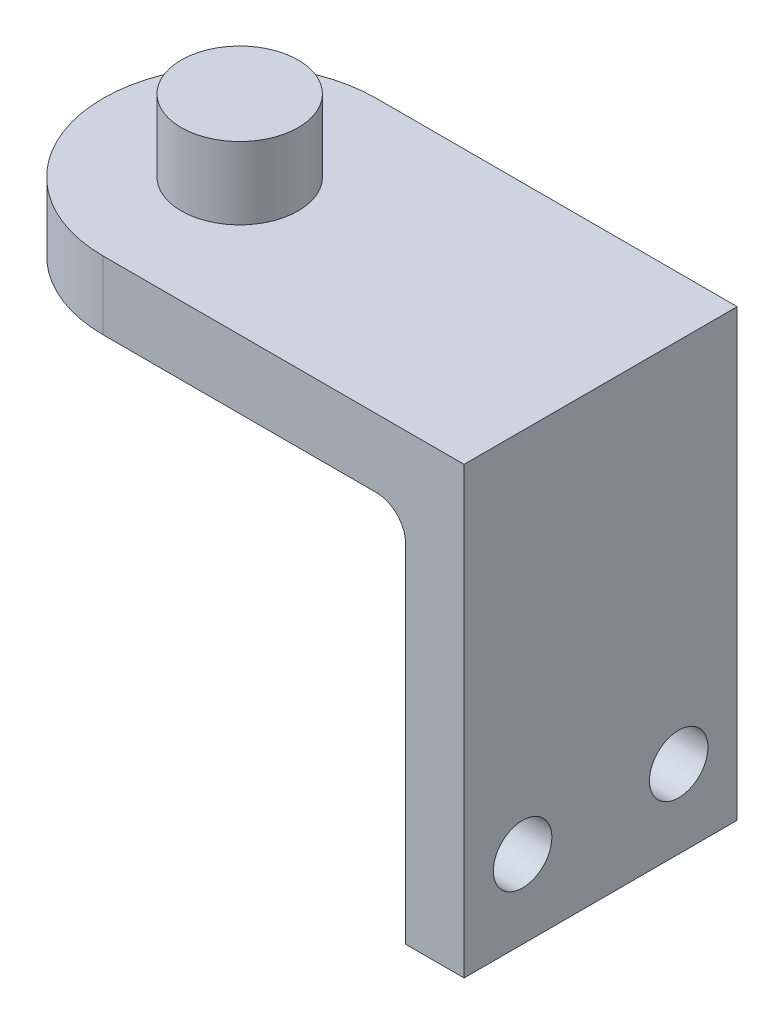
SolidWorks part; units mm, degrees
material "ABS"
ref_plane "Front Plane" through (0, 0, 0) normal (0, 0, 1) x (1, 0, 0)
ref_plane "Top Plane" through (0, 0, 0) normal (0, 1, 0) x (1, 0, 0)
ref_plane "Right Plane" through (0, 0, 0) normal (1, 0, 0) x (0, 0, -1)
ref_plane "Y+19_30" through (0, 19.3, 0) normal (0, 1, 0) x (1, 0, 0)
sketch "Sketch1" plane through (0, 19.3, 0) normal (0, 1, 0) x (1, 0, 0)
  line L0 (5.5, -7) -> (24, -7)
  line L1 (24, -7) -> (24, 7)
  line L2 (24, 7) -> (5.5, 7)
  arc A0 (5.5, 7) -> (5.5, -7) centre (5.5, 0) ccw
extrude "Boss-Extrude1" add sketch "Sketch1" along normal blind 3.5
sketch "Sketch2" plane through (0, 0, 0) normal (0, 0, 1) x (1, 0, 0)
  line L1 (21, 0) -> (24, 0)
  line L2 (21, 0) -> (21, 22.8)
  line L3 (21, 22.8) -> (24, 22.8)
  line L4 (24, 0) -> (24, 22.8)
extrude "Boss-Extrude2" add sketch "Sketch2" along normal mid plane 14
ref_plane "Y+22_80" through (0, 22.8, 0) normal (0, 1, 0) x (1, 0, 0)
sketch "Sketch3" plane through (0, 22.8, 0) normal (0, 1, 0) x (1, 0, 0)
  circle A0 centre (5.5, 0) radius 3
extrude "Boss-Extrude3" add sketch "Sketch3" along normal blind 3.7
sketch "Sketch4" plane through (0, 19.3, 0) normal (0, 1, 0) x (1, 0, 0)
  circle A0 centre (5.5, 0) radius 3.7
extrude "Cut-Extrude2" cut sketch "Sketch4" along normal blind 1.6
sketch "Sketch5" plane through (0, 19.3, 0) normal (0, 1, 0) x (1, 0, 0)
  line L0 (5.5, -2.7) -> (20.7, -2.7)
  line L1 (20.7, -2.7) -> (20.7, 2.7)
  line L2 (20.7, 2.7) -> (5.5, 2.7)
  arc A0 (5.5, 2.7) -> (5.5, -2.7) centre (5.5, 0) ccw
extrude "Cut-Extrude4" cut sketch "Sketch5" along normal blind 1.6
sketch "Sketch6" plane through (0, 0, 0) normal (0, 1, 0) x (1, 0, 0)
  line L1 (21.9, -6.7) -> (23.1, -6.7)
  line L2 (21.9, -6.7) -> (21.9, 6.7)
  line L3 (21.9, 6.7) -> (23.1, 6.7)
  line L4 (23.1, -6.7) -> (23.1, 6.7)
extrude "Cut-Extrude6" cut sketch "Sketch6" along normal blind 2.2
ref_plane "X_LINK" through (24, 0, 0) normal (1, 0, 0) x (0, 0, -1)
sketch "Sketch7" plane through (24, 0, 0) normal (1, 0, 0) x (0, 0, -1)
  circle A0 centre (-4, 4) radius 1.5
  circle A1 centre (4, 4) radius 1.5
extrude "Cut-Extrude7" cut sketch "Sketch7" against normal blind 3
fillet "Fillet1" radius 1.5 1 edges at (21, 19.3, 0) tangent propagation no
